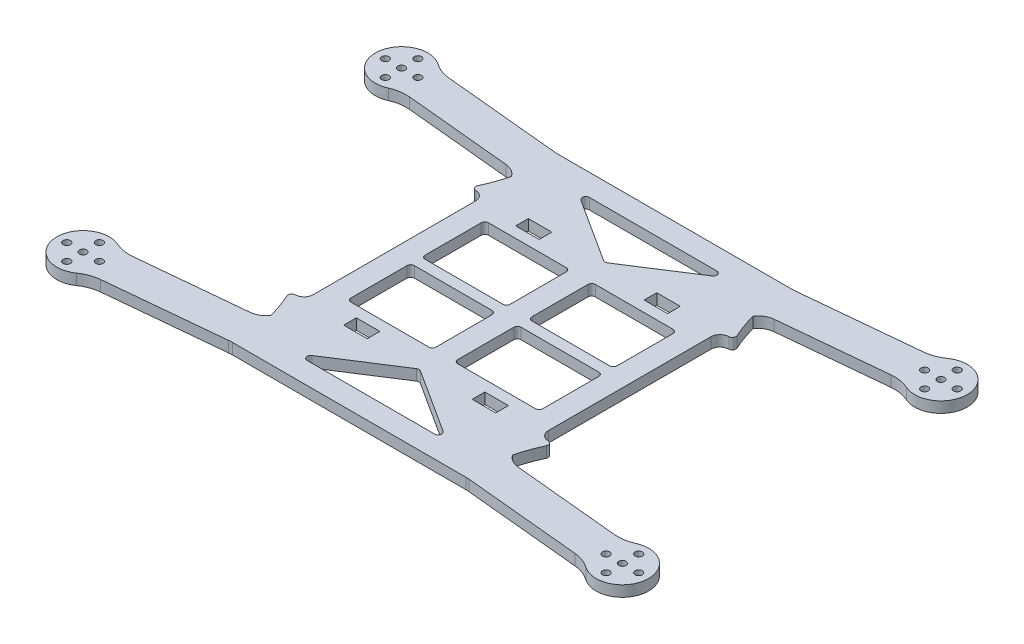
SolidWorks part; units mm, degrees
material "PLA"
ref_plane "Front Plane" through (0, 0, 0) normal (0, 0, 1) x (1, 0, 0)
ref_plane "Top Plane" through (0, 0, 0) normal (0, 1, 0) x (1, 0, 0)
ref_plane "Right Plane" through (0, 0, 0) normal (1, 0, 0) x (0, 0, -1)
sketch "Sketch1" plane through (0, 0, 0) normal (0, 1, 0) x (1, 0, 0)
  line L0 (-65.5414, 48.1601) -> (-33.2187, 45.0461)
  line L1 (-32.2597, -45) -> (32.2597, -45)
  line L2 (-32.5, -22.4419) -> (-32.5, 22.4419)
  line L3 (-32.2597, 45) -> (32.2597, 45)
  line L4 (32.5, -22.4419) -> (32.5, 22.4419)
  line L5 (0, 45) -> (0, -45) construction
  line L6 (-32.5, 0) -> (32.5, 0) construction
  line L7 (-66.5004, 38.2062) -> (-37.0205, 35.3661)
  line L8 (-74.5, 44) -> (-32.5933, 39.9627) construction
  line L9 (-74.5, -44) -> (-32.5933, -39.9627) construction
  line L10 (0, -55) -> (0, 55) construction
  line L11 (-66.5004, -38.2062) -> (-37.0205, -35.3661)
  line L12 (-65.5414, -48.1601) -> (-33.2187, -45.0461)
  line L13 (74.5, -44) -> (32.5933, -39.9627) construction
  line L14 (65.5414, -48.1601) -> (33.2187, -45.0461)
  line L15 (66.5004, -38.2062) -> (37.0205, -35.3661)
  line L16 (74.5, 44) -> (32.5933, 39.9627) construction
  line L17 (66.5004, 38.2062) -> (37.0205, 35.3661)
  line L18 (65.5414, 48.1601) -> (33.2187, 45.0461)
  arc A34 (-70.3318, 49.932) -> (-71.5409, 37.3814) centre (-74.5, 44) ccw
  circle A35 centre (-74.5, 44) radius 4.5 construction
  circle A36 centre (-79, 44) radius 1
  circle A49 centre (79, -44) radius 1
  circle A55 centre (79, 44) radius 1
  arc A58 (-33.3868, 33.2319) -> (-37.0205, 35.3661) centre (-37.5, 30.3891) ccw
  arc A59 (-32.2597, 45) -> (-33.2187, 45.0461) centre (-32.2597, 55) cw
  circle A60 centre (-74.5, 48.5) radius 1
  circle A61 centre (-70, 44) radius 1
  circle A62 centre (-74.5, 39.5) radius 1
  arc A63 (-66.5004, 38.2062) -> (-71.5409, 37.3814) centre (-67.4593, 28.2522) ccw
  arc A64 (-70.3318, 49.932) -> (-65.5414, 48.1601) centre (-64.5824, 58.114) ccw
  arc A65 (-33.3868, -33.2319) -> (-37.0205, -35.3661) centre (-37.5, -30.3891) cw
  circle A66 centre (-74.5, -44) radius 4.5 construction
  arc A67 (-70.3318, -49.932) -> (-65.5414, -48.1601) centre (-64.5824, -58.114) cw
  arc A68 (-66.5004, -38.2062) -> (-71.5409, -37.3814) centre (-67.4593, -28.2522) cw
  circle A69 centre (-74.5, -39.5) radius 1
  circle A70 centre (-70, -44) radius 1
  circle A71 centre (-74.5, -48.5) radius 1
  arc A72 (-32.2597, -45) -> (-33.2187, -45.0461) centre (-32.2597, -55) ccw
  circle A73 centre (-79, -44) radius 1
  arc A74 (-70.3318, -49.932) -> (-71.5409, -37.3814) centre (-74.5, -44) cw
  circle A75 centre (74.5, -44) radius 4.5 construction
  arc A76 (70.3318, -49.932) -> (71.5409, -37.3814) centre (74.5, -44) ccw
  circle A77 centre (79, -44) radius 1
  arc A78 (32.2597, -45) -> (33.2187, -45.0461) centre (32.2597, -55) cw
  circle A79 centre (74.5, -48.5) radius 1
  circle A80 centre (70, -44) radius 1
  circle A81 centre (74.5, -39.5) radius 1
  arc A82 (66.5004, -38.2062) -> (71.5409, -37.3814) centre (67.4593, -28.2522) ccw
  arc A83 (70.3318, -49.932) -> (65.5414, -48.1601) centre (64.5824, -58.114) ccw
  arc A84 (33.3868, -33.2319) -> (37.0205, -35.3661) centre (37.5, -30.3891) ccw
  circle A85 centre (74.5, 44) radius 4.5 construction
  arc A86 (70.3318, 49.932) -> (65.5414, 48.1601) centre (64.5824, 58.114) cw
  arc A87 (66.5004, 38.2062) -> (71.5409, 37.3814) centre (67.4593, 28.2522) cw
  circle A88 centre (74.5, 39.5) radius 1
  circle A89 centre (70, 44) radius 1
  circle A90 centre (74.5, 48.5) radius 1
  arc A91 (32.2597, 45) -> (33.2187, 45.0461) centre (32.2597, 55) ccw
  arc A92 (33.3868, 33.2319) -> (37.0205, 35.3661) centre (37.5, 30.3891) cw
  circle A93 centre (79, 44) radius 1
  arc A94 (70.3318, 49.932) -> (71.5409, 37.3814) centre (74.5, 44) cw
  circle A95 centre (-74.5, -44) radius 1
  circle A96 centre (-74.5, 44) radius 1
  circle A97 centre (74.5, 44) radius 1
  circle A98 centre (74.5, -44) radius 1
  arc A99 (-35.8354, 26.3563) -> (-33.3868, 33.2319) centre (-74.5, 44) ccw
  arc A100 (-32.5, 22.4419) -> (-34.9469, 24.9414) centre (-35, 22.4419) ccw
  arc A101 (-35.8354, 26.3563) -> (-34.9469, 24.9414) centre (-34.9257, 25.9411) ccw
  arc A102 (35.8354, 26.3563) -> (33.3868, 33.2319) centre (74.5, 44) cw
  arc A103 (32.5, 22.4419) -> (34.9469, 24.9414) centre (35, 22.4419) cw
  arc A104 (35.8354, 26.3563) -> (34.9469, 24.9414) centre (34.9257, 25.9411) cw
  arc A105 (35.8354, -26.3563) -> (33.3868, -33.2319) centre (74.5, -44) ccw
  arc A106 (35.8354, -26.3563) -> (34.9469, -24.9414) centre (34.9257, -25.9411) ccw
  arc A107 (32.5, -22.4419) -> (34.9469, -24.9414) centre (35, -22.4419) ccw
  arc A108 (-35.8354, -26.3563) -> (-34.9469, -24.9414) centre (-34.9257, -25.9411) cw
  arc A109 (-32.5, -22.4419) -> (-34.9469, -24.9414) centre (-35, -22.4419) cw
  arc A110 (-35.8354, -26.3563) -> (-33.3868, -33.2319) centre (-74.5, -44) cw
  point P0 (0, 0)
  point P23 (-32.7403, 45)
  point P28 (-70, 70)
  point P40 (-74.5, 44)
  point P66 (-74.5, -44)
  point P68 (-70, -70)
  point P69 (-32.7403, -45)
  point P90 (32.7403, -45)
  point P91 (74.5, -44)
  point P113 (74.5, 44)
  point P114 (70, 70)
  point P115 (32.7403, 45)
  dimension "D3" = 44
  dimension "D5" = 45
  dimension "D8" = 14.5
  dimension "D9" = 10
  dimension "D10" = 2
  dimension "D4" = 64.5194
  dimension "D7" = 32.5
  dimension "D6" = 6.364
  dimension "D11" = 9
  dimension "D12" = 2
  dimension "D13" = 10
  dimension "D14" = 85
  dimension "D15" = 5
  dimension "D18" = 10
  dimension "D20" = 10
  dimension "D21" = 10
  dimension "D22" = 2
  dimension "D16" = 65
  dimension "D17" = 5
  dimension "D19" = 4
extrude "Boss-Extrude1" add sketch "Sketch1" along normal blind 3 contours A94 A86 L18 A91 L3 A59 L0 A64 A34 A63 L7 A58 L2 A65 L11 A68 A74 A67 L12 A72 L1 A78 L14 A83 A76 A82 L15 A84 L4 A92 L17 A87 A89 A73 A70 A55 A36 A49 A60 A61 A62 region at (0, 0, 0)
sketch "Sketch2" plane through (0, 3, 0) normal (0, 1, 0) x (1, 0, 0)
  line L0 (-1.65, 0) -> (1.65, 0) construction
  line L1 (-21, 25.5) -> (-14.5, 25.5)
  line L2 (-21, 25.5) -> (-21, 22)
  line L3 (-21, 22) -> (-14.5, 22)
  line L4 (-14.5, 25.5) -> (-14.5, 22)
  line L5 (-14.5, -25.5) -> (-14.5, -22)
  line L6 (-21, -22) -> (-14.5, -22)
  line L7 (-21, -25.5) -> (-21, -22)
  line L8 (-21, -25.5) -> (-14.5, -25.5)
  line L9 (0, -1.65) -> (0, 1.65) construction
  line L10 (21, -25.5) -> (14.5, -25.5)
  line L11 (21, -25.5) -> (21, -22)
  line L12 (21, -22) -> (14.5, -22)
  line L13 (14.5, -25.5) -> (14.5, -22)
  line L14 (14.5, 25.5) -> (14.5, 22)
  line L15 (21, 22) -> (14.5, 22)
  line L16 (21, 25.5) -> (21, 22)
  line L17 (21, 25.5) -> (14.5, 25.5)
  line L18 (-25.5, 19) -> (-4, 19)
  line L19 (-25.5, -1.5) -> (-4, -1.5)
  line L20 (-26.5, -2.5) -> (-26.5, -18)
  line L21 (-25.5, -19) -> (-4, -19)
  line L22 (-3, -2.5) -> (-3, -18)
  line L23 (-26.5, 18) -> (-26.5, 2.5)
  line L24 (-25.5, 1.5) -> (-4, 1.5)
  line L25 (-3, 18) -> (-3, 2.5)
  line L26 (4, 19) -> (25.5, 19)
  line L27 (3, 18) -> (3, 2.5)
  line L28 (4, 1.5) -> (25.5, 1.5)
  line L29 (26.5, 18) -> (26.5, 2.5)
  line L30 (4, -1.5) -> (25.5, -1.5)
  line L31 (3, -2.5) -> (3, -18)
  line L32 (4, -19) -> (25.5, -19)
  line L33 (26.5, -2.5) -> (26.5, -18)
  line L34 (-32.5, -22.4419) -> (-32.5, 22.4419) construction
  line L35 (32.5, -22.4419) -> (32.5, 22.4419) construction
  line L36 (-17.5952, 39) -> (17.5952, 39)
  line L37 (18.1359, 37.1588) -> (0.5408, 25.8476)
  line L38 (-0.5408, 25.8476) -> (-18.1359, 37.1588)
  line L39 (-32.2597, 45) -> (32.2597, 45) construction
  line L40 (-17.5952, -39) -> (17.5952, -39)
  line L41 (18.1359, -37.1588) -> (0.5408, -25.8476)
  line L42 (-0.5408, -25.8476) -> (-18.1359, -37.1588)
  line L43 (-32.2597, -45) -> (32.2597, -45) construction
  arc A0 (0.5408, -25.8476) -> (-0.5408, -25.8476) centre (0, -26.6888) ccw
  arc A1 (17.5952, -39) -> (18.1359, -37.1588) centre (17.5952, -38) ccw
  arc A2 (-17.5952, -39) -> (-18.1359, -37.1588) centre (-17.5952, -38) cw
  arc A3 (26.5, -18) -> (25.5, -19) centre (25.5, -18) cw
  arc A4 (26.5, -2.5) -> (25.5, -1.5) centre (25.5, -2.5) ccw
  arc A5 (3, -2.5) -> (4, -1.5) centre (4, -2.5) cw
  arc A6 (3, -18) -> (4, -19) centre (4, -18) ccw
  arc A7 (-25.5, -19) -> (-26.5, -18) centre (-25.5, -18) cw
  arc A8 (-3, -18) -> (-4, -19) centre (-4, -18) cw
  arc A9 (-3, -2.5) -> (-4, -1.5) centre (-4, -2.5) ccw
  arc A10 (-25.5, -1.5) -> (-26.5, -2.5) centre (-25.5, -2.5) ccw
  arc A11 (-25.5, 1.5) -> (-26.5, 2.5) centre (-25.5, 2.5) cw
  arc A12 (-3, 18) -> (-4, 19) centre (-4, 18) ccw
  arc A13 (-26.5, 18) -> (-25.5, 19) centre (-25.5, 18) cw
  arc A14 (-3, 2.5) -> (-4, 1.5) centre (-4, 2.5) cw
  arc A15 (3, 2.5) -> (4, 1.5) centre (4, 2.5) ccw
  arc A16 (26.5, 2.5) -> (25.5, 1.5) centre (25.5, 2.5) cw
  arc A17 (26.5, 18) -> (25.5, 19) centre (25.5, 18) ccw
  arc A18 (4, 19) -> (3, 18) centre (4, 18) ccw
  arc A19 (18.1359, 37.1588) -> (17.5952, 39) centre (17.5952, 38) ccw
  arc A20 (-17.5952, 39) -> (-18.1359, 37.1588) centre (-17.5952, 38) ccw
  arc A21 (0.5408, 25.8476) -> (-0.5408, 25.8476) centre (0, 26.6888) cw
  point P53 (0, -25.5)
  point P56 (21, -39)
  point P59 (-21, -39)
  point P68 (3, -19)
  point P73 (-3, -19)
  point P96 (21, 39)
  point P99 (-21, 39)
  point P102 (0, 25.5)
  dimension "D21" = 1
  dimension "D1" = 3.5
  dimension "D2" = 6.5
  dimension "D3" = 14.5
  dimension "D4" = 22
  dimension "D5" = 6
  dimension "D6" = 6
  dimension "D7" = 6
  dimension "D8" = 3
  dimension "D9" = 3
  dimension "D10" = 3
  dimension "D11" = 3
  dimension "D12" = 6
  dimension "D13" = 3
  dimension "D14" = 3
  dimension "D15" = 6
  dimension "D16" = 6
  dimension "D17" = 3
  dimension "D18" = 1.5
  dimension "D19" = 1.5
  dimension "D20" = 6
  dimension "D23" = 42
  dimension "D24" = 6
extrude "Cut-Extrude1" cut sketch "Sketch2" against normal blind 3
